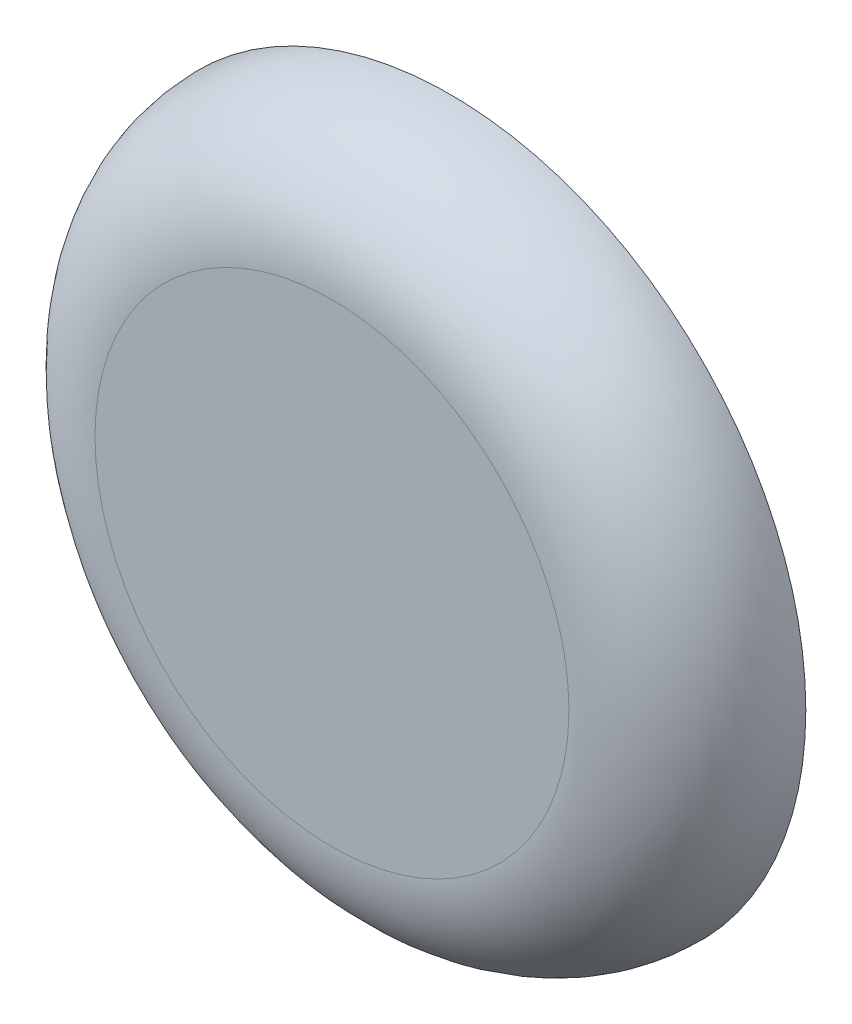
SolidWorks part; units mm, degrees
ref_plane "Front Plane" through (0, 0, 0) normal (0, 0, 1) x (1, 0, 0)
ref_plane "Top Plane" through (0, 0, 0) normal (0, 1, 0) x (1, 0, 0)
ref_plane "Right Plane" through (0, 0, 0) normal (1, 0, 0) x (0, 0, -1)
sketch "Sketch1" plane through (0, 0, 0) normal (0, 0, 1) x (1, 0, 0)
  circle A0 centre (0, 0) radius 6
  dimension "D1" = 12
extrude "Boss-Extrude1" add sketch "Sketch1" along normal blind 2
fillet "Fillet2" radius 2 1 edges at (6, 0, 2)
